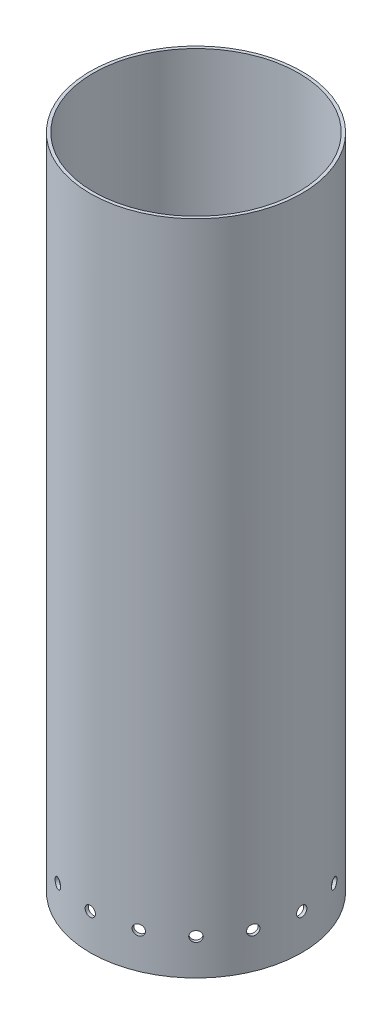
SolidWorks part; units mm, degrees
ref_plane "Front Plane" through (0, 0, 0) normal (0, 0, 1) x (1, 0, 0)
ref_plane "Top Plane" through (0, 0, 0) normal (0, 1, 0) x (1, 0, 0)
ref_plane "Right Plane" through (0, 0, 0) normal (1, 0, 0) x (0, 0, -1)
sketch "Sketch1" plane through (0, 0, 0) normal (0, 1, 0) x (1, 0, 0)
  circle A0 centre (0, 0) radius 63.5
  circle A1 centre (0, 0) radius 65.405
  dimension "D1" = 127
  dimension "D2" = 130.81
extrude "Boss-Extrude1" add sketch "Sketch1" against normal blind 406.4
ref_plane "Plane1" through (0, 0, 65.405) normal (0, 0, 1) x (1, 0, 0)
ref_axis "Axis1" through (0, -406.4, 0) along (0, 1, 0)
sketch "Sketch4" plane through (0, 0, 65.405) normal (0, 0, 1) x (1, 0, 0)
  line L2 (-65.405, -406.4) -> (65.405, -406.4) construction
  circle A0 centre (0, -384.175) radius 3.175
  point P0 (0, -384.175)
  point P8 (0, 0)
  dimension "D2" = 6.35
  dimension "D1" = 22.225
extrude "Cut-Extrude3" cut sketch "Sketch4" against normal up to next
pattern_circular "CirPattern2" count 16 over 360 about axis through (0, -406.4, 0) along (0, 1, 0) of "Cut-Extrude3"
